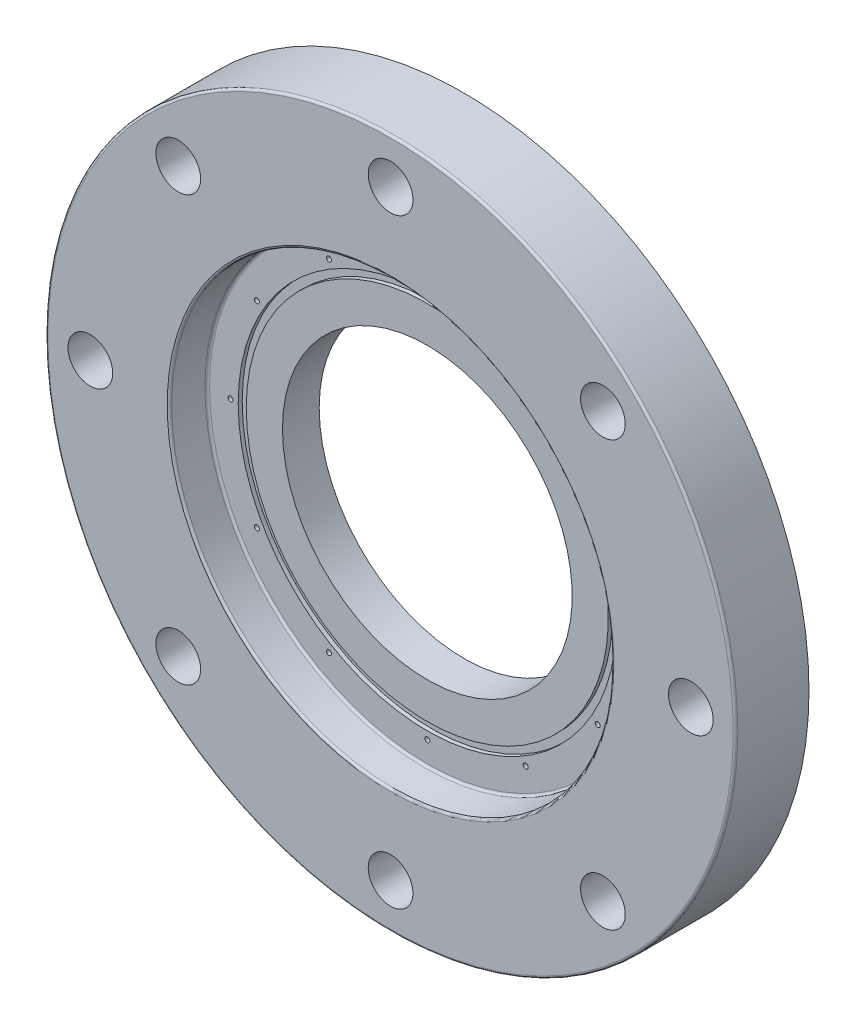
SolidWorks part; units mm, degrees
ref_plane "Front Plane" through (0, 0, 0) normal (0, 0, 1) x (1, 0, 0)
ref_plane "Top Plane" through (0, 0, 0) normal (0, 1, 0) x (1, 0, 0)
ref_plane "Right Plane" through (0, 0, 0) normal (1, 0, 0) x (0, 0, -1)
sketch "Sketch0" plane through (0, 0, 0) normal (1, 0, 0) x (0, 0, -1)
  line L0 (0, 0) -> (-36.5125, 0) construction
  point P3 (-36.5125, 0)
  point P4 (-5.5562, 0)
  dimension "Q" = 36.5125
  dimension "N" = 5.5562
sketch "Sketch1" plane through (0, 0, 0) normal (0, 0, 1) x (1, 0, 0)
  circle A0 centre (0, 0) radius 171.45
  circle A1 centre (0, 0) radius 109.9185 construction
  circle A2 centre (0, 0) radius 149.225 construction
  circle A3 centre (0, 149.225) radius 11.1125 construction
  circle A6 centre (0, 0) radius 109.347 construction
  point P9 (0, 109.9185)
  point P10 (0, 109.347)
  dimension "A" = 342.9
  dimension "B" = 298.45
  dimension "Bolt Hole Size" = 22.225
  dimension "Pipe OD A" = 219.837
  dimension "Pipe OD B" = 218.694
extrude "Extrude1" add sketch "Sketch1" along normal up to vertex (36.5125 mm away) up to point (0, 0, 36.5125)
sketch "Sketch2" plane through (0, 0, 36.5125) normal (0, 0, 1) x (1, 0, 0)
  circle A0 centre (0, 149.225) radius 11.1125 construction
  circle A1 centre (0, 149.225) radius 11.1125
extrude "Extrude2" cut sketch "Sketch2" against normal through all
ref_axis "Axis1" through (0, 0, -1.6272) along (0, 0, 1)
pattern_circular "CirPattern1" count 8 over 360 about axis through (0, 0, -1.6272) along (0, 0, 1) of "Extrude2"
sketch "Sketch3" plane through (0, 0, 0) normal (1, 0, 0) x (0, 0, -1)
  line L0 (-36.5125, 109.9185) -> (-18.2563, 109.347)
  line L1 (-18.2563, 109.347) -> (-18.2562, 0)
  line L2 (0, 0) -> (-36.5125, 0) construction
  line L3 (-18.2562, 0) -> (-36.5125, 0)
  line L4 (-36.5125, 0) -> (-36.5125, 109.9185)
  line L5 (0, 109.347) -> (-18.2563, 109.347) construction
  line L6 (-36.5125, 109.9185) -> (0, 109.9185) construction
revolve "Cut-Revolve1" cut sketch "Sketch3" angle 360 about L3
fillet "Fillet1" radius 1.1545 3 edges at (171.45, 0, 36.5125) (0, 109.347, 18.2563) (0, 109.9185, 36.5125) tangent propagation no
sketch "Sketch4" plane through (0, 0, 0) normal (0, 0, -1) x (-1, 0, 0)
  circle A0 centre (0, 0) radius 72
  dimension "D1" = 144
extrude "Cut-Extrude1" cut sketch "Sketch4" against normal blind 120 contours A0
sketch "Sketch5" plane through (0, 0, 18.2562) normal (0, 0, -1) x (-1, 0, 0)
  circle A0 centre (0, 0) radius 90
  circle A1 centre (0, 0) radius 94
sketch "Sketch6" plane through (0, 0, 18.2562) normal (0, 0, -1) x (-1, 0, 0)
  line L0 (0, 0) -> (0, 85) construction
  circle A0 centre (0, 0) radius 85 construction
  point P3 (0, 85)
  dimension "D1" = 170
hole_wizard "M3x0.5 Tapped Hole1" positions "Sketch7" profile "Sketch8" tap size "M3x0.5" standard "ANSI Metric"
sketch "Sketch7" plane through (0, 0, 18.2562) normal (0, 0, -1) x (-1, 0, 0)
  point P0 (0, 97.79)
sketch "Sketch8" plane through (0, 97.79, 18.2562) normal (1, 0, 0) x (0, -1, 0)
  line L0 (0, 0) -> (0, 12.7511)
  line L1 (0, 12.7511) -> (1.25, 12)
  line L2 (1.25, 12) -> (1.25, 0)
  line L5 (1.25, 0) -> (0, 0)
  line L10 (0, 12.7511) -> (-1.25, 12) construction
  line L11 (0, -6.35) -> (0, 107.95) construction
  dimension "Tap Drill Dia." = 2.5
  dimension "Tap Drill Depth" = 12
  dimension "Drill Angle" = 118
cosmetic thread "Hole Thread1" parameters "D1"=6, "D2"=3
sketch "Sketch9" plane through (0, 0, 0) normal (0, 1, 0) x (1, 0, 0)
  line L0 (0, 0) -> (0, 111.6244) construction
pattern_circular "CirPattern2" count 12 over 360 about axis through (0, 0, 0) along (0, 0, -1) of "M3x0.5 Tapped Hole1"
extrude "Cut-Extrude2" cut sketch "Sketch5" along normal blind 2
